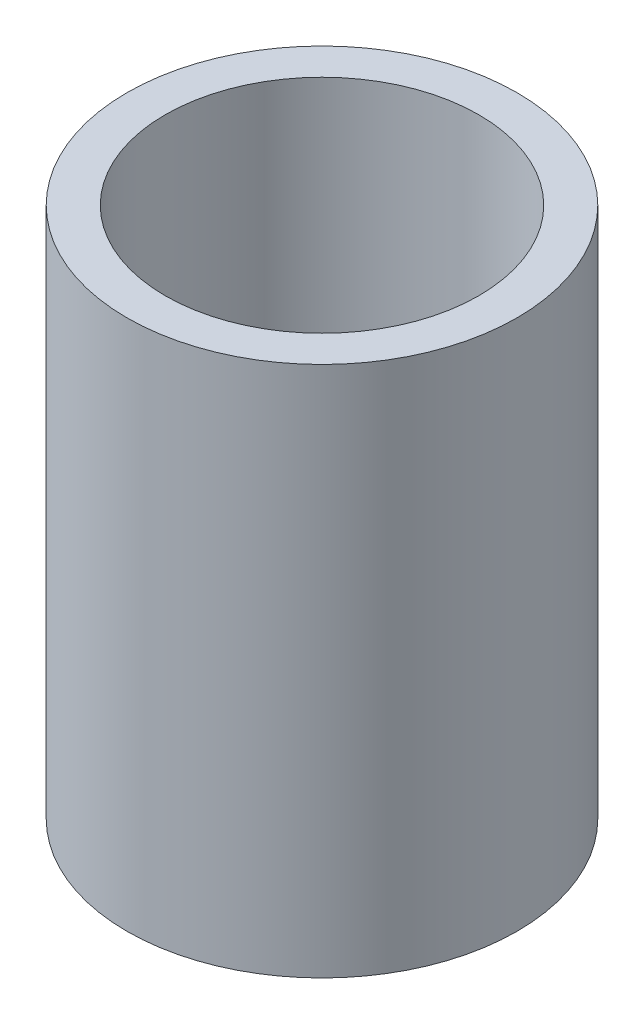
SolidWorks part; units mm, degrees
material "6061-T6 (SS)"
ref_plane "Front Plane" through (0, 0, 0) normal (0, 0, 1) x (1, 0, 0)
ref_plane "Top Plane" through (0, 0, 0) normal (0, 1, 0) x (1, 0, 0)
ref_plane "Right Plane" through (0, 0, 0) normal (1, 0, 0) x (0, 0, -1)
sketch "Sketch1" plane through (0, 0, 0) normal (0, 1, 0) x (1, 0, 0)
  circle A0 centre (0, 0) radius 5.1054
  circle A1 centre (0, 0) radius 6.35
  dimension "D1" = 10.2108
  dimension "D2" = 12.7
extrude "Boss-Extrude1" add sketch "Sketch1" along normal blind 17.3
